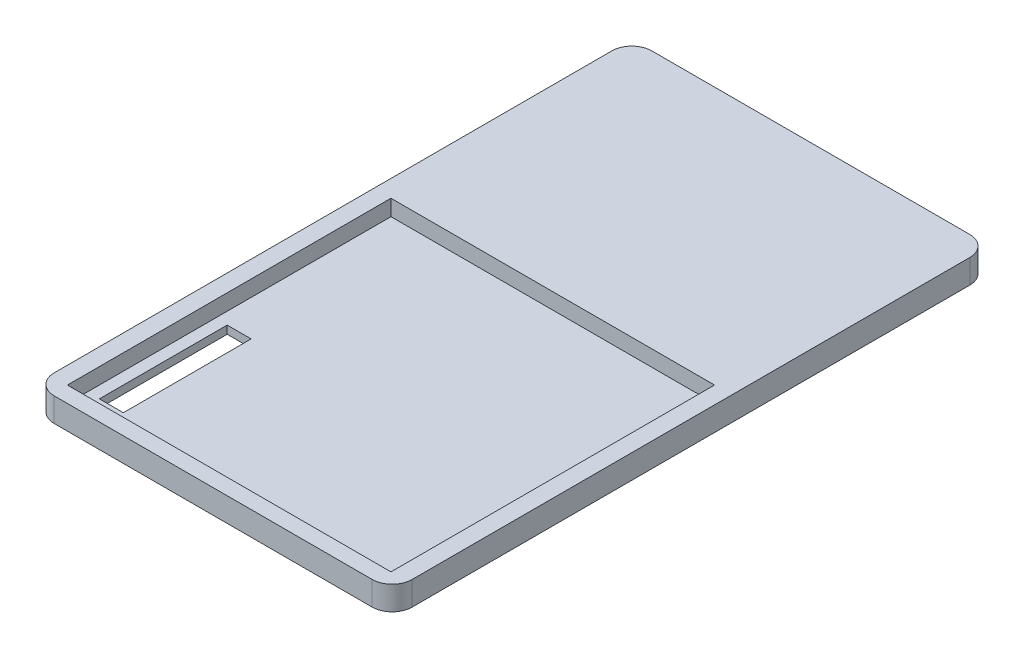
SolidWorks part; units mm, degrees
ref_plane "Front Plane" through (0, 0, 0) normal (0, 0, 1) x (1, 0, 0)
ref_plane "Top Plane" through (0, 0, 0) normal (0, 1, 0) x (1, 0, 0)
ref_plane "Right Plane" through (0, 0, 0) normal (1, 0, 0) x (0, 0, -1)
sketch "Sketch1" plane through (0, 0, 0) normal (0, 1, 0) x (1, 0, 0)
  line L0 (0, 37.4) -> (0, -37.4) construction
  line L1 (-19.9, 37.4) -> (19.9, 37.4)
  line L2 (-22.4, 34.9) -> (-22.4, -34.9)
  line L3 (-19.9, -37.4) -> (19.9, -37.4)
  line L4 (22.4, 34.9) -> (22.4, -34.9)
  line L5 (-22.4, 0) -> (22.4, 0) construction
  line L6 (-15.75, -16.9) -> (-18.75, -16.9)
  line L7 (-20.25, 5.1) -> (20.25, 5.1)
  line L8 (-20.25, 5.1) -> (-20.25, -35.4)
  line L9 (-20.25, -35.4) -> (20.25, -35.4)
  line L10 (20.25, 5.1) -> (20.25, -35.4)
  line L14 (-15.75, -16.9) -> (-15.75, -32.9)
  line L15 (-18.75, -16.9) -> (-18.75, -32.9)
  line L16 (-18.75, -32.9) -> (-15.75, -32.9)
  arc A0 (-22.4, -34.9) -> (-19.9, -37.4) centre (-19.9, -34.9) ccw
  arc A1 (19.9, -37.4) -> (22.4, -34.9) centre (19.9, -34.9) ccw
  arc A2 (22.4, 34.9) -> (19.9, 37.4) centre (19.9, 34.9) ccw
  arc A3 (-19.9, 37.4) -> (-22.4, 34.9) centre (-19.9, 34.9) ccw
  point P15 (-22.4, -37.4)
  point P20 (22.4, 37.4)
  point P23 (-22.4, 37.4)
  point P28 (0, 0)
  dimension "D3" = 2.5
  dimension "D1" = 44.8
  dimension "D2" = 74.8
  dimension "D4" = 40.5
  dimension "D5" = 40.5
  dimension "D6" = 2
  dimension "D7" = 16
  dimension "D8" = 4.5
  dimension "D9" = 3
  dimension "D10" = 2.5
extrude "Boss-Extrude1" add sketch "Sketch1" along normal blind 3 contours L1 A3 L2 A0 L3 A1 L4 A2 L7 L10 L9 L8 region at (0, 0, -14.571)
extrude "Boss-Extrude2" add sketch "Sketch1<3>" along normal blind 1 contours L10 L7 L8 L9 L16 L15 L6 L14 region at (0.52, 0, 14.8561)
sketch "Sketch1<3>" plane through (0, 0, 0) normal (0, 1, 0) x (1, 0, 0) same geometry as "Sketch1"
